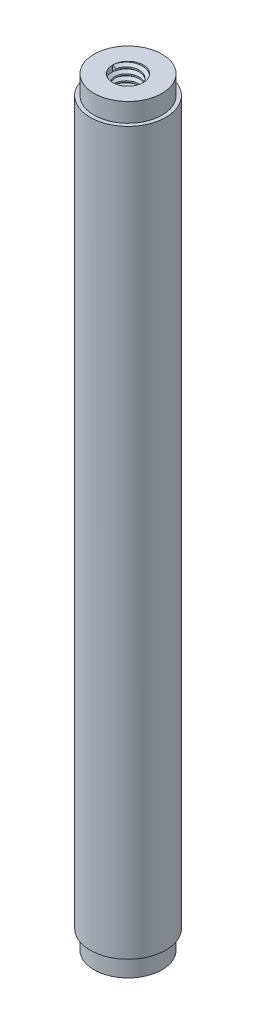
SolidWorks part; units mm, degrees
ref_plane "Front Plane" through (0, 0, 0) normal (0, 0, 1) x (1, 0, 0)
ref_plane "Top Plane" through (0, 0, 0) normal (0, 1, 0) x (1, 0, 0)
ref_plane "Right Plane" through (0, 0, 0) normal (1, 0, 0) x (0, 0, -1)
sketch "Sketch1" plane through (0, 0, 0) normal (0, 1, 0) x (1, 0, 0)
  circle A0 centre (0, 0) radius 5
extrude "Boss-Extrude1" add sketch "Sketch1" along normal blind 100.5
sketch "Sketch5" plane through (0, 0, 0) normal (0, -1, 0) x (1, 0, 0)
  circle A0 centre (0, 0) radius 2.025
extrude "Cut-Extrude1" cut sketch "Sketch5" against normal blind 25.4 contours A0
thread "Thread1" pitch 0.7937 profile "Thread Profile3" start angle 0, offset 0, length 38.1, pitch 0.7937, diameter 4.05
ref_plane "Plane3" through (2.025, 0, 0) normal (0, 0, 1) x (1, 0, 0)
sketch "Thread Profile3" plane through (2.025, 0, 0) normal (0, 0, 1) x (1, 0, 0)
  line L0 (0, 0) -> (0, 0.7937) construction
  line L11 (0, 0) -> (0, 0.6945)
  line L12 (0, 0.6945) -> (-0.4296, 0.4465)
  line L13 (-0.4296, 0.4465) -> (-0.4296, 0.248)
  line L15 (-0.4296, 0.248) -> (0, 0)
  line L17 (-0.4296, 0.3473) -> (0, 0.3473) construction
  point P2 (0, 0)
  dimension "Pitch" = 0.7937
  dimension "Profile_Angle" = 60
  dimension "Profile_Land" = 0.1984
  dimension "Profile_Height" = 0.4296
sketch "Sketch19" plane through (0, 100.5, 0) normal (0, 1, 0) x (1, 0, 0)
  circle A0 centre (0, 0) radius 2.025
extrude "Cut-Extrude2" cut sketch "Sketch19" against normal blind 25.4
thread "Thread2" pitch 0.7937 profile "Thread Profile4" start angle 0, offset 0, length 38.1, pitch 0.7937, diameter 4.05
ref_plane "Plane4" through (-2.025, 100.5, 0) normal (0, 0, 1) x (-1, 0, 0)
sketch "Thread Profile4" plane through (-2.025, 100.5, 0) normal (0, 0, 1) x (-1, 0, 0)
  line L0 (0, 0) -> (0, 0.7937) construction
  line L11 (0, 0) -> (0, 0.6945)
  line L12 (0, 0.6945) -> (-0.4296, 0.4465)
  line L13 (-0.4296, 0.4465) -> (-0.4296, 0.248)
  line L15 (-0.4296, 0.248) -> (0, 0)
  line L17 (-0.4296, 0.3473) -> (0, 0.3473) construction
  point P2 (0, 0)
  dimension "Pitch" = 0.7937
  dimension "Profile_Angle" = 60
  dimension "Profile_Land" = 0.1984
  dimension "Profile_Height" = 0.4296
sketch "Sketch24" plane through (0, 0, 0) normal (0, -1, 0) x (-1, 0, 0)
  circle A0 centre (0, 0) radius 5
  circle A1 centre (0, 0) radius 4.5
  dimension "D1" = 0.5
extrude "Cut-Extrude3" cut sketch "Sketch24" against normal blind 2.5
sketch "Sketch25" plane through (0, 100.5, 0) normal (0, 1, 0) x (1, 0, 0)
  circle A0 centre (0, 0) radius 5
  circle A1 centre (0, 0) radius 4.5
  dimension "D1" = 0.5
extrude "Cut-Extrude4" cut sketch "Sketch25" against normal blind 2.5
